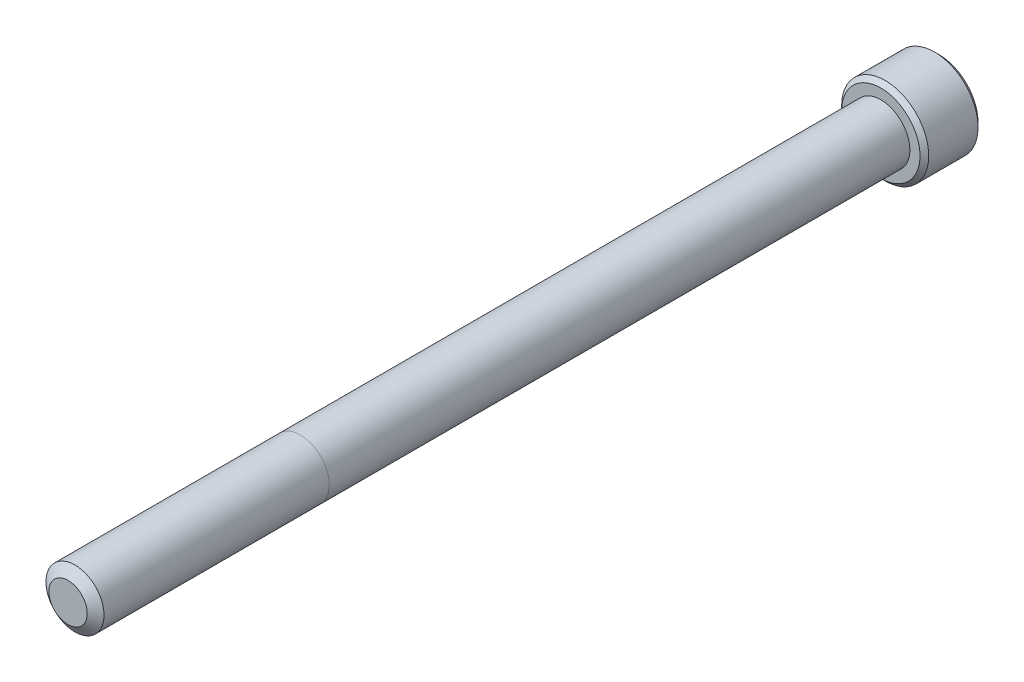
SolidWorks part; units mm, degrees
ref_plane "Front Plane" through (0, 0, 0) normal (0, 0, 1) x (1, 0, 0)
ref_plane "Top Plane" through (0, 0, 0) normal (0, 1, 0) x (1, 0, 0)
ref_plane "Right Plane" through (0, 0, 0) normal (1, 0, 0) x (0, 0, -1)
sketch "Sketch1" plane through (0, 0, 0) normal (0, 0, 1) x (1, 0, 0)
  circle A0 centre (0, 0) radius 3.175
  dimension "OD" = 6.35
extrude "Extrude1" add sketch "Sketch1" against normal blind 88.9
sketch "Sketch2" plane through (0, 0, 0) normal (0, 0, 1) x (1, 0, 0)
  circle A0 centre (0, 0) radius 3.175 construction
  circle A1 centre (0, 0) radius 3.175
curve "Helix/Spiral1" [suppressed] pitch 1.27 height 90.17 turns 71 parameters "pitch"=1.27
sketch "Sketch3" plane through (0, 0, 0) normal (1, 0, 0) x (0, 0, -1)
  line L0 (-1.1113, 3.175) -> (-0.635, 2.3501)
  line L1 (-0.635, 2.3501) -> (-0.4763, 2.3501)
  line L2 (-0.4763, 2.3501) -> (0, 3.175)
  line L3 (-1.1113, 3.175) -> (0, 3.175)
  line L4 (-0.5556, 3.175) -> (-0.5556, 2.3501) construction
  line L5 (-0.8731, 2.7626) -> (-0.2381, 2.7626) construction
  line L6 (0, 3.175) -> (0, -3.175) construction
  dimension "D1" = 0.1588
  dimension "D2" = 0.635
  dimension "D3" = 60
sweep "Cut-Sweep1" [suppressed] cut profiles "Sketch3" path "Helix/Spiral1"
sketch "Sketch4" plane through (0, 0, 0) normal (1, 0, 0) x (0, 0, -1)
  line L0 (0.7554, 3.175) -> (0, 2.0961)
  line L1 (0, 2.0961) -> (0, 3.175)
  line L2 (0.7554, 3.175) -> (0, 3.175)
  line L3 (-1.1113, 3.175) -> (0, 3.175) construction
  line L4 (0, 0) -> (7.0209, 0) construction
  dimension "D1" = 55
  dimension "D2" = 0.254
revolve "Cut-Revolve1" cut sketch "Sketch4" angle 360 about L4
sketch "Sketch5" [suppressed] plane through (0, 0, 0) normal (1, 0, 0) x (0, 0, -1)
  line L0 (88.9, -2.3728) -> (88.9, 2.2654) construction
  line L1 (88.9, 3.302) -> (25.5202, 3.302)
  line L2 (88.9, 3.302) -> (88.9, 0)
  line L3 (88.9, 0) -> (25.4, 0)
  line L4 (25.4, 2.9718) -> (25.4, 0)
  line L5 (25.5202, 3.302) -> (25.4, 2.9718)
  line L6 (0, 0) -> (9.9695, 0) construction
  point P3 (25.4, 3.302)
  point P10 (25.4, 3.302)
  dimension "D1" = 0.3302
  dimension "Thread min" = 25.4
  dimension "D2" = 0.127
  dimension "D3" = 20
revolve "partially thread" [suppressed] add sketch "Sketch5" angle 360 about L6
sketch "Sketch6" plane through (0, 0, -88.9) normal (0, 0, -1) x (-1, 0, 0)
  circle A0 centre (0, 0) radius 4.7625
  dimension "head dia" = 9.525
extrude "Extrude2" add sketch "Sketch6" along normal blind 6.35
sketch "Sketch7" plane through (0, 0, -95.25) normal (0, 0, -1) x (-1, 0, 0)
  line L1 (0, 2.7496) -> (-2.3812, 1.3748)
  line L2 (-2.3812, 1.3748) -> (-2.3813, -1.3748)
  line L3 (-2.3813, -1.3748) -> (0, -2.7496)
  line L4 (0, -2.7496) -> (2.3812, -1.3748)
  line L5 (2.3812, -1.3748) -> (2.3812, 1.3748)
  line L6 (2.3812, 1.3748) -> (0, 2.7496)
  circle A0 centre (0, 0) radius 2.3813 construction
  dimension "hex dia" = 4.7625
extrude "Cut-Extrude1" cut sketch "Sketch7" against normal blind 3.5719
sketch "Sketch8" plane through (0, 0, -95.25) normal (0, 0, -1) x (-1, 0, 0)
  circle A0 centre (0, 0) radius 2.7496
extrude "Cut-Extrude2" cut sketch "Sketch8" against normal through all draft 45
chamfer "Chamfer1" distance 0.4763 angle 45 2 edges at (-4.7625, 0, -95.25) (-4.7625, 0, -88.9)
sketch "Sketch9" plane through (0, 0, 0) normal (1, 0, 0) x (0, 0, -1)
  line L0 (0, 3.175) -> (0, -3.175) construction
  line L1 (6.985, 3.175) -> (6.985, -3.175) construction
  dimension "D1" = 6.985
sketch "Sketch10" plane through (0, 0, 0) normal (0, 1, 0) x (1, 0, 0)
  line L0 (-3.175, 25.4) -> (3.175, 25.4)
  line L1 (-3.175, 88.9) -> (-3.175, 0.7554) construction
  line L2 (3.175, 0.7554) -> (3.175, 88.9) construction
  line L3 (-2.0961, 0) -> (2.0961, 0) construction
  dimension "D1" = 25.4
split line "Split Line1"
equation "\"D3@Helix/Spiral1\" = \"screw length@Extrude1\"+\"pitch@Helix/Spiral1\""
equation "\"D1@Sketch3\" = \"pitch@Helix/Spiral1\"*.125"
equation "\"D2@Sketch3\" = \"pitch@Helix/Spiral1\"*.5"
equation "\"D1@Cut-Extrude1\" = \"hex dia@Sketch7\"*.75"
equation "\"D1@Chamfer1\" = \"head dia@Sketch6\"*.05"
equation "\"D1@Sketch9\" = \"pitch@Helix/Spiral1\"*5.5"
